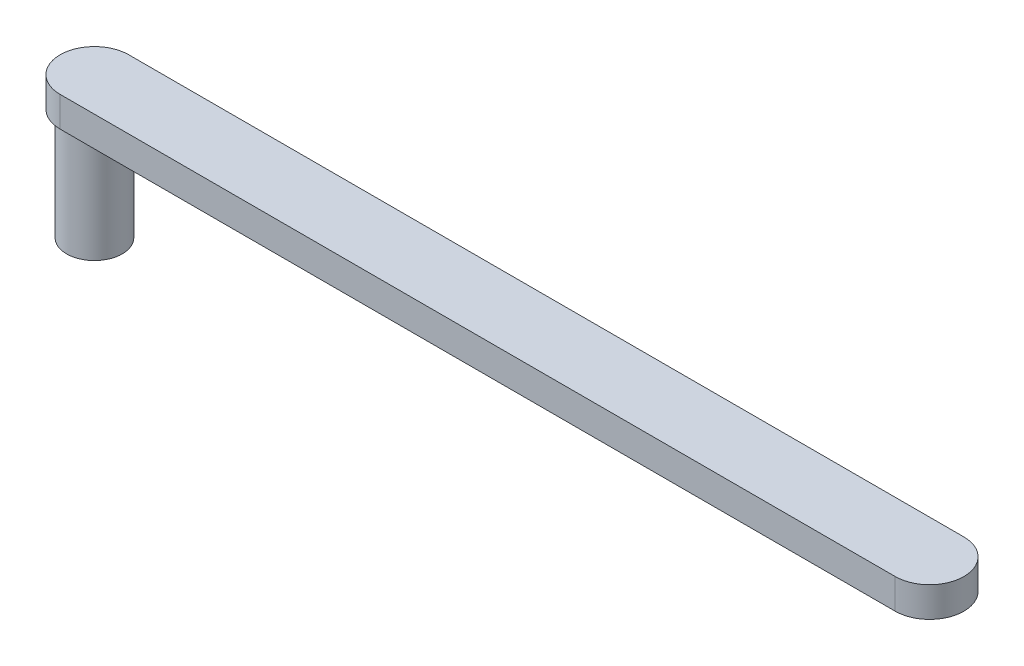
SolidWorks part; units mm, degrees
ref_plane "Front Plane" through (0, 0, 0) normal (0, 0, 1) x (1, 0, 0)
ref_plane "Top Plane" through (0, 0, 0) normal (0, 1, 0) x (1, 0, 0)
ref_plane "Right Plane" through (0, 0, 0) normal (1, 0, 0) x (0, 0, -1)
sketch "Sketch1" plane through (0, 0, 0) normal (0, 1, 0) x (1, 0, 0)
  circle A0 centre (0, 0) radius 12.7
extrude "Boss-Extrude1" add sketch "Sketch1" along normal blind 50.8
sketch "Sketch2" plane through (0, 50.8, 0) normal (0, 1, 0) x (1, 0, 0)
  line L0 (0, 0) -> (381, 0) construction
  line L1 (0, 15.6553) -> (381, 15.6553)
  line L2 (0, -15.6553) -> (381, -15.6553)
  arc A0 (0, 15.6553) -> (0, -15.6553) centre (0, 0) ccw
  arc A1 (381, -15.6553) -> (381, 15.6553) centre (381, 0) ccw
  point P3 (190.5, 0)
extrude "Boss-Extrude2" add sketch "Sketch2" along normal blind 13.716
ref_axis "Axis2" through (0, 50.8, 0) along (0, -1, 0)
